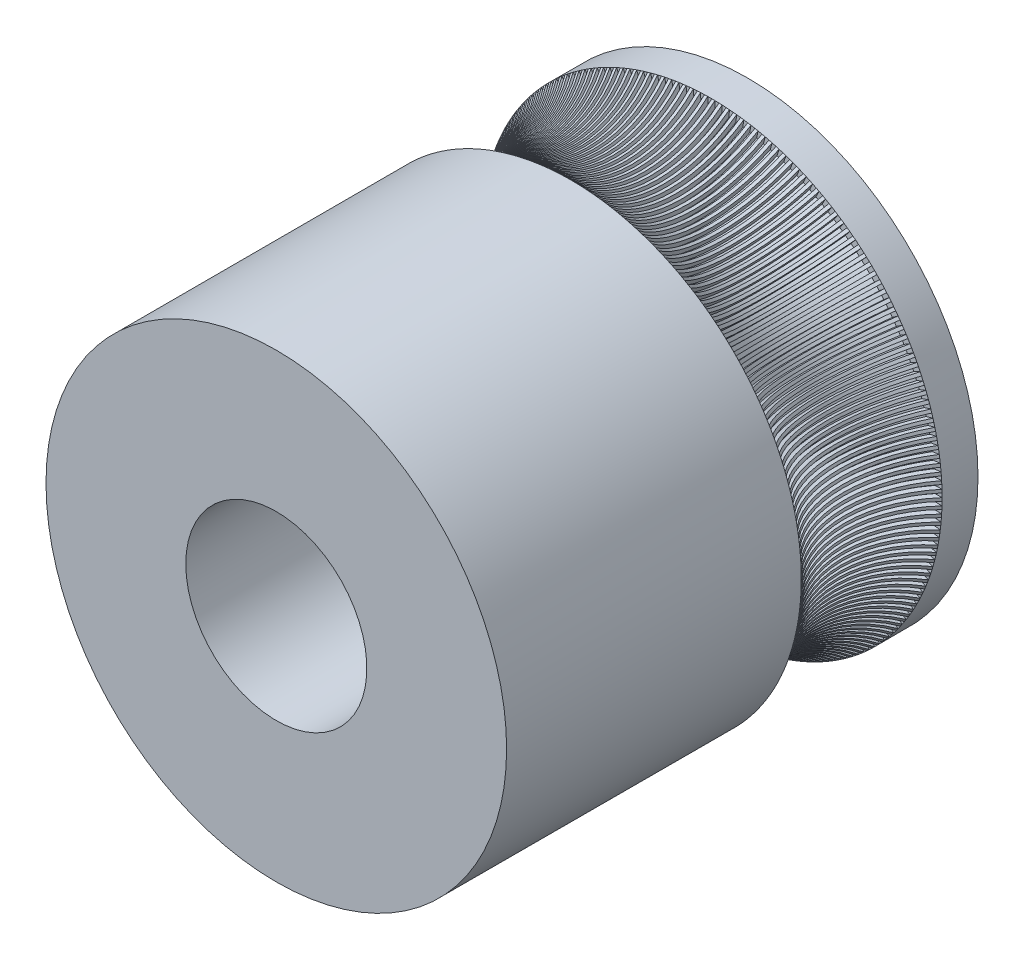
SolidWorks part; units mm, degrees
ref_plane "Front Plane" through (0, 0, 0) normal (0, 0, 1) x (1, 0, 0)
ref_plane "Top Plane" through (0, 0, 0) normal (0, 1, 0) x (1, 0, 0)
ref_plane "Right Plane" through (0, 0, 0) normal (1, 0, 0) x (0, 0, -1)
sketch "Sketch1" plane through (0, 0, 0) normal (0, 1, 0) x (1, 0, 0)
  line L0 (0, 0) -> (0, -8.2) construction
  line L1 (0, -8.2) -> (-2.52, -8.2) construction
  line L2 (0, 0) -> (-6.41, 0) construction
  line L3 (-2.52, -8.2) -> (-2.52, 4.92)
  line L4 (-2.52, 4.92) -> (-6.41, 4.92)
  line L5 (-2.52, -8.2) -> (-6.41, -8.2)
  line L6 (-6.41, 4.92) -> (-6.41, 3.92)
  line L7 (-6.41, -8.2) -> (-6.41, 0)
  line L8 (-6.41, 3.92) -> (-6.41, 0) construction
  line L9 (-2.52, 1.96) -> (0, 1.96) construction
  line L10 (0, 1.96) -> (-6.41, 1.96) construction
  arc A0 (-6.41, 3.92) -> (-6.41, 0) centre (-8.6194, 1.96) cw
  dimension "D1" = 2.9535
  dimension "D2" = 2.52
  dimension "D3" = 6.41
  dimension "D4" = 8.6194
  dimension "D5" = 4.92
  dimension "D6" = 8.2
revolve "Revolve1" add sketch "Sketch1" angle 360 about L0 other way angle 360
sketch "Sketch2" plane through (0, 0, 0) normal (0, 1, 0) x (1, 0, 0)
  line L0 (-6.41, 3.92) -> (-6.2132, 3.92)
  line L1 (-6.41, 0) -> (-6.2132, 0)
  line L2 (-6.41, 0) -> (6.41, 0) construction
  line L3 (0, 0) -> (0, -13.2292) construction
  arc A0 (-6.41, 0) -> (-6.41, 3.92) centre (-8.6194, 1.96) ccw construction
  arc A1 (-6.41, 0) -> (-6.41, 3.92) centre (-8.6194, 1.96) ccw
  arc A2 (-6.2132, 0) -> (-6.2132, 3.92) centre (-8.6194, 1.96) ccw
  arc A3 (-6.2978, -0.0995) -> (-6.2978, 4.0195) centre (-8.6194, 1.96) ccw construction
  dimension "D1" = 0.15
revolve "Cut-Revolve1" cut sketch "Sketch2" angle 1 about L3
ref_axis "Axis1" through (0, 0, -8.936) along (0, 0, 1)
pattern_circular "CirPattern1" count 200 over 360 about axis through (0, 0, -8.936) along (0, 0, 1) of "Cut-Revolve1"
